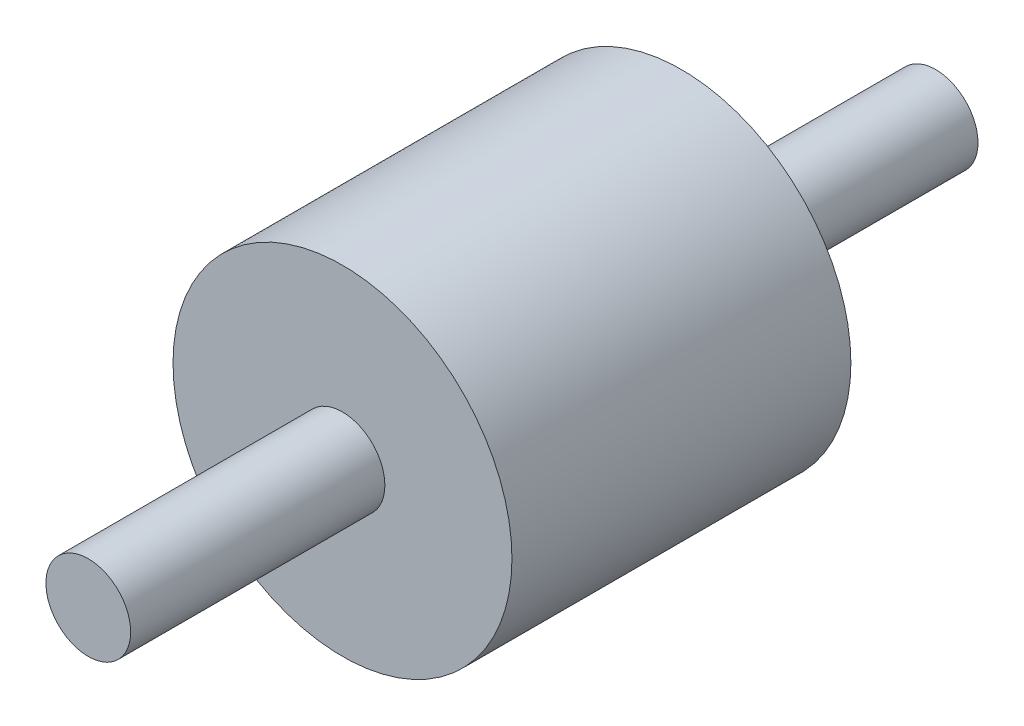
SolidWorks part; units mm, degrees
ref_plane "Plan de face" through (0, 0, 0) normal (0, 0, 1) x (1, 0, 0)
ref_plane "Plan de dessus" through (0, 0, 0) normal (0, 1, 0) x (1, 0, 0)
ref_plane "Plan de droite" through (0, 0, 0) normal (1, 0, 0) x (0, 0, -1)
sketch "Esquisse1" plane through (0, 0, 0) normal (0, 0, 1) x (1, 0, 0)
  circle A0 centre (0, 0) radius 4
  dimension "D1" = 8
extrude "Boss.-Extru.1" add sketch "Esquisse1" along normal blind 4 and the other way blind 4
sketch "Esquisse2" plane through (0, 0, 0) normal (0, 0, 1) x (1, 0, 0)
  circle A0 centre (0, 0) radius 1
  circle A1 centre (0, 0) radius 4 construction
  dimension "D1" = 2
extrude "Boss.-Extru.2" add sketch "Esquisse2" along normal blind 10 and the other way blind 10
